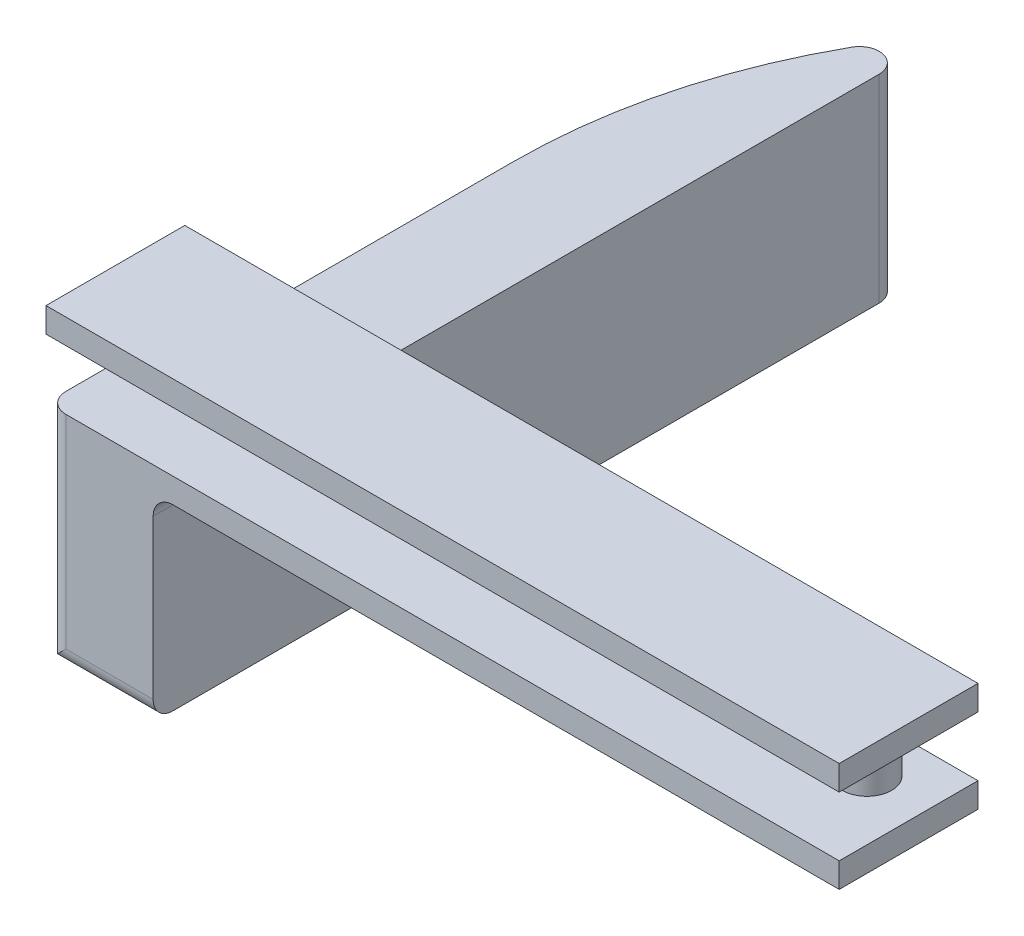
SolidWorks part; units mm, degrees
ref_plane "Front Plane" through (0, 0, 0) normal (0, 0, 1) x (1, 0, 0)
ref_plane "Top Plane" through (0, 0, 0) normal (0, 1, 0) x (1, 0, 0)
ref_plane "Right Plane" through (0, 0, 0) normal (1, 0, 0) x (0, 0, -1)
sketch "Sketch2" plane through (0, 0, 0) normal (0, 1, 0) x (1, 0, 0)
  line L1 (0, 0) -> (101.6, 0)
  line L2 (0, 0) -> (0, 17.78)
  line L3 (0, 17.78) -> (101.6, 17.78)
  line L4 (101.6, 0) -> (101.6, 17.78)
  dimension "D1" = 17.78
  dimension "D2" = 101.6
extrude "Boss-Extrude1" add sketch "Sketch2" along normal blind 3.175
sketch "Sketch3" plane through (0, 0, 0) normal (0, -1, 0) x (1, 0, 0)
  line L0 (93.98, -11.176) -> (5.08, -11.176) construction
  line L1 (93.98, -14.351) -> (5.08, -14.351)
  line L2 (93.98, -8.001) -> (5.08, -8.001)
  line L3 (0, 0) -> (101.6, 0) construction
  line L4 (0, -17.78) -> (0, 0) construction
  arc A0 (93.98, -14.351) -> (93.98, -8.001) centre (93.98, -11.176) ccw
  arc A1 (5.08, -8.001) -> (5.08, -14.351) centre (5.08, -11.176) ccw
  point P2 (49.53, -11.176)
  dimension "D1" = 88.9
  dimension "D2" = 11.176
  dimension "D3" = 5.08
  dimension "D4" = 6.35
extrude "Boss-Extrude2" add sketch "Sketch3" along normal blind 7.62 contours L2 A1 L1 A0
ref_plane "Plane1" through (0, -3.81, 0) normal (0, -1, 0) x (-1, 0, 0)
mirror "Mirror1" about plane through (0, -3.81, 0) normal (0, -1, 0) of "Boss-Extrude1"
sketch "Sketch5" plane through (0, -10.795, 0) normal (0, -1, 0) x (1, 0, 0)
  line L31 (0, 0) -> (13.7244, 0)
  line L32 (0, 0) -> (0, -59.8993)
  line L36 (13.7244, 0) -> (13.7244, -101.6)
  arc A2 (0, -59.8993) -> (13.7244, -101.6) centre (70.2144, -59.8993) ccw
  dimension "D1" = 101.6
extrude "Boss-Extrude3" add sketch "Sketch5" along normal blind 25.4
fillet "Fillet2" radius 2.54 1 edges at (13.7244, -23.495, -101.6)
fillet "Fillet3" radius 2.54 3 edges at (13.7244, -10.795, -8.89) (0, -21.9075, 0) (6.8622, -36.195, 0)
